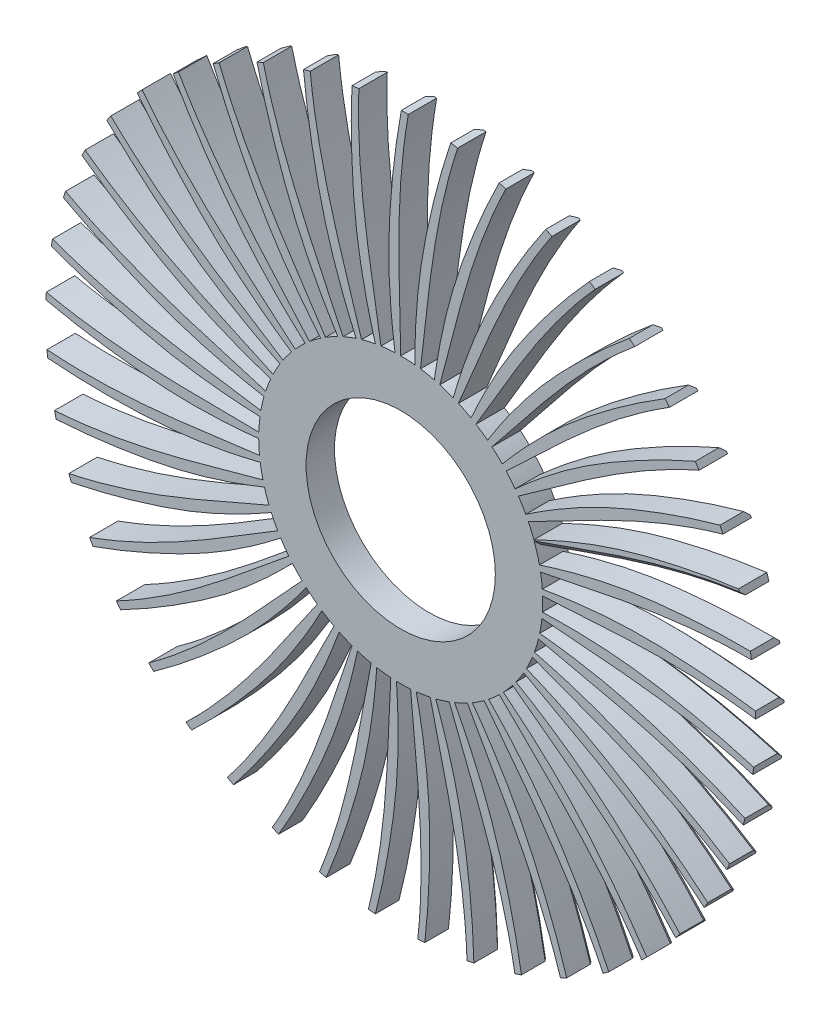
SolidWorks part; units mm, degrees
ref_plane "Front Plane" through (0, 0, 0) normal (0, 0, 1) x (1, 0, 0)
ref_plane "Top Plane" through (0, 0, 0) normal (0, 1, 0) x (1, 0, 0)
ref_plane "Right Plane" through (0, 0, 0) normal (1, 0, 0) x (0, 0, -1)
sketch "Sketch2" plane through (0, 0, 0) normal (0, 0, 1) x (1, 0, 0)
  arc A0 (-367.8181, 73.0398) -> (-369.1843, 65.7869) centre (0, 0) ccw
  arc A1 (-6, 149.88) -> (-20.876, 148.5402) centre (0, 0) ccw
  arc A2 (-354.0734, 123.5194) -> (-356.4357, 116.5272) centre (0, 0) ccw
  arc A3 (-333.437, 171.5948) -> (-336.7494, 164.9994) centre (0, 0) ccw
  arc A4 (-273.2223, 256.8552) -> (-278.2243, 251.4284) centre (0, 0) ccw
  arc A5 (-234.816, 292.3807) -> (-240.5246, 287.7028) centre (0, 0) ccw
  arc A6 (-191.8392, 322.2153) -> (-198.1433, 318.3775) centre (0, 0) ccw
  arc A7 (-145.1286, 345.7784) -> (-151.9054, 342.8553) centre (0, 0) ccw
  arc A8 (-95.5931, 362.6113) -> (-102.7109, 360.6598) centre (0, 0) ccw
  arc A9 (-44.1971, 372.3864) -> (-51.5172, 371.4445) centre (0, 0) ccw
  arc A10 (8.0592, 374.9134) -> (0.6793, 374.9994) centre (0, 0) ccw
  arc A11 (60.1586, 370.1431) -> (52.8625, 371.2554) centre (0, 0) ccw
  arc A12 (111.0871, 358.1685) -> (104.0168, 360.2853) centre (0, 0) ccw
  arc A13 (159.8535, 339.2224) -> (153.1465, 342.3027) centre (0, 0) ccw
  arc A14 (205.5084, 313.6739) -> (199.2955, 317.6576) centre (0, 0) ccw
  arc A15 (247.1634, 282.02) -> (241.5653, 286.8296) centre (0, 0) ccw
  arc A16 (284.0076, 244.8769) -> (279.1334, 250.4188) centre (0, 0) ccw
  arc A17 (315.3239, 202.9675) -> (311.2684, 209.1338) centre (0, 0) ccw
  arc A18 (340.5028, 157.1076) -> (337.345, 163.7784) centre (0, 0) ccw
  arc A19 (359.0543, 108.1898) -> (356.8555, 115.2352) centre (0, 0) ccw
  arc A20 (370.6171, 57.1662) -> (369.4203, 64.449) centre (0, 0) ccw
  arc A21 (372.0172, -47.2042) -> (372.8741, -39.8737) centre (0, 0) ccw
  arc A22 (374.9663, 5.03) -> (374.7947, 12.4084) centre (0, 0) ccw
  arc A23 (361.8272, -98.5196) -> (363.696, -91.3797) centre (0, 0) ccw
  arc A24 (344.5946, -147.9174) -> (347.4389, -141.1071) centre (0, 0) ccw
  arc A25 (320.6549, -194.4362) -> (324.4194, -188.088) centre (0, 0) ccw
  arc A26 (254.6394, -275.2885) -> (260.0078, -270.2238) centre (0, 0) ccw
  arc A27 (290.474, -237.1705) -> (295.0853, -231.408) centre (0, 0) ccw
  arc A28 (213.8485, -308.0484) -> (219.8696, -303.7801) centre (0, 0) ccw
  arc A29 (168.8953, -334.8124) -> (175.4518, -331.4237) centre (0, 0) ccw
  arc A30 (120.6547, -355.0598) -> (127.619, -352.6165) centre (0, 0) ccw
  arc A31 (-300.3975, -224.469) -> (-295.9218, -230.3374) centre (0, 0) ccw
  arc A32 (-350.6327, -132.9727) -> (-347.9478, -139.8474) centre (0, 0) ccw
  arc A33 (-328.7141, -180.4772) -> (-325.0986, -186.9114) centre (0, 0) ccw
  arc A34 (-373.702, -31.1741) -> (-373.0161, -38.5226) centre (0, 0) ccw
  arc A35 (70.0658, -368.3962) -> (77.3023, -366.946) centre (0, 0) ccw
  arc A36 (18.1131, -374.5623) -> (25.481, -374.1333) centre (0, 0) ccw
  arc A37 (-34.1922, -373.4379) -> (-26.8363, -374.0385) centre (0, 0) ccw
  arc A38 (-85.832, -365.045) -> (-78.6312, -366.6635) centre (0, 0) ccw
  arc A39 (-135.8011, -349.5469) -> (-128.8957, -352.1518) centre (0, 0) ccw
  arc A40 (-183.127, -327.2453) -> (-176.6513, -330.7859) centre (0, 0) ccw
  arc A41 (-226.8886, -298.5742) -> (-220.9687, -302.9816) centre (0, 0) ccw
  arc A42 (-266.234, -264.0917) -> (-260.9851, -269.2801) centre (0, 0) ccw
  arc A43 (-374.4037, 21.1386) -> (-374.7472, 13.7662) centre (0, 0) ccw
  arc A44 (-306.3106, 216.3303) -> (-310.5087, 210.2601) centre (0, 0) ccw
  arc A46 (-26.8009, 147.5863) -> (-41.3456, 144.1893) centre (0, 0) ccw
  arc A47 (-47.0801, 142.42) -> (-61.0105, 137.0318) centre (0, 0) ccw
  arc A48 (35.5449, 145.7277) -> (20.876, 148.5402) centre (0, 0) ccw
  arc A49 (14.9176, 149.2564) -> (0, 150) centre (0, 0) ccw
  arc A50 (-66.4429, 134.4817) -> (-79.4879, 127.2072) centre (0, 0) ccw
  arc A51 (-84.5126, 123.9259) -> (-96.4181, 114.9067) centre (0, 0) ccw
  arc A52 (-100.9372, 110.958) -> (-111.4717, 100.3696) centre (0, 0) ccw
  arc A53 (55.4804, 139.3626) -> (41.3456, 144.1893) centre (0, 0) ccw
  arc A54 (74.336, 130.2849) -> (61.0105, 137.0318) centre (0, 0) ccw
  arc A55 (91.7447, 118.6714) -> (79.4879, 127.2072) centre (0, 0) ccw
  arc A56 (-115.3973, 95.8304) -> (-124.3556, 83.8789) centre (0, 0) ccw
  arc A57 (-127.6113, 78.8376) -> (-134.8191, 65.7557) centre (0, 0) ccw
  arc A58 (107.3677, 104.7481) -> (96.4181, 114.9067) centre (0, 0) ccw
  arc A59 (120.901, 88.786) -> (111.4717, 100.3696) centre (0, 0) ccw
  arc A60 (132.081, 71.0958) -> (124.3556, 83.8789) centre (0, 0) ccw
  arc A61 (-137.3414, 60.3103) -> (-142.6585, 46.3525) centre (0, 0) ccw
  arc A62 (140.6902, 52.0218) -> (134.8191, 65.7557) centre (0, 0) ccw
  arc A63 (146.561, 31.9352) -> (142.6585, 46.3525) centre (0, 0) ccw
  arc A64 (-144.3984, 40.6091) -> (-147.7212, 26.0472) centre (0, 0) ccw
  arc A65 (-148.6448, 20.1175) -> (-149.9086, 5.2349) centre (0, 0) ccw
  arc A66 (-149.998, -0.7656) -> (-149.1783, -15.6793) centre (0, 0) ccw
  arc A67 (-148.4317, -21.6339) -> (-145.5444, -36.2883) centre (0, 0) ccw
  arc A68 (-143.9763, -42.081) -> (-139.0776, -56.191) centre (0, 0) ccw
  arc A69 (-136.7186, -61.7091) -> (-129.9038, -75) centre (0, 0) ccw
  arc A70 (-126.7998, -80.1361) -> (-118.2016, -92.3492) centre (0, 0) ccw
  arc A71 (-114.413, -97.0034) -> (-104.1988, -107.901) centre (0, 0) ccw
  arc A72 (-99.7993, -111.9826) -> (-88.1678, -121.3525) centre (0, 0) ccw
  arc A73 (-83.2431, -124.7821) -> (-70.4207, -132.4421) centre (0, 0) ccw
  arc A74 (-65.0667, -135.153) -> (-51.303, -140.9539) centre (0, 0) ccw
  arc A75 (-45.6238, -142.8932) -> (-31.1868, -146.7221) centre (0, 0) ccw
  arc A76 (-25.2929, -147.8522) -> (-10.4635, -149.6346) centre (0, 0) ccw
  arc A77 (-4.4697, -149.9334) -> (10.4635, -149.6346) centre (0, 0) ccw
  arc A78 (16.4405, -149.0963) -> (31.1868, -146.7221) centre (0, 0) ccw
  arc A79 (37.0307, -145.3572) -> (51.303, -140.9539) centre (0, 0) ccw
  arc A80 (56.9001, -138.789) -> (70.4207, -132.4421) centre (0, 0) ccw
  arc A81 (75.6621, -129.5193) -> (88.1678, -121.3525) centre (0, 0) ccw
  arc A82 (108.4314, -103.6467) -> (118.2016, -92.3492) centre (0, 0) ccw
  arc A83 (121.801, -87.5472) -> (129.9038, -75) centre (0, 0) ccw
  arc A84 (132.7998, -69.7438) -> (139.0776, -56.191) centre (0, 0) ccw
  arc A85 (141.2139, -50.5829) -> (145.5444, -36.2883) centre (0, 0) ccw
  arc A86 (146.8794, -30.4375) -> (149.1783, -15.6793) centre (0, 0) ccw
  arc A87 (92.9513, -117.7287) -> (104.1988, -107.901) centre (0, 0) ccw
  arc A88 (149.6861, -9.6996) -> (149.9086, 5.2349) centre (0, 0) ccw
  arc A89 (149.5793, 11.2271) -> (147.7212, 26.0472) centre (0, 0) ccw
  arc A90 (-365.7266, -82.8799) -> (-364.0246, -90.0615) centre (0, 0) ccw
  spline S0 degree 3 poles (-6, 149.88) (-14.2223, 209.3858) (-13.9632, 258.2908) (-6.2485, 332.5828) (-2.5507, 357.9172) (0.6793, 374.9994) knots 0 0 0 0 0.599001 0.688647 0.89646 0.89646 0.89646 0.89646
  spline S1 degree 3 poles (0, 150) (-1.5677, 225.8182) (-6.3003, 293.9271) (8.0592, 374.9134) knots 0 0 0 0 0.908524 0.908524 0.908524 0.908524
  spline S2 degree 3 poles (14.9176, 149.2564) (15.0569, 209.3274) (22.1198, 257.7204) (40.0988, 330.2157) (47.2865, 354.789) (52.8625, 371.2554) knots 0 0 0 0 0.599001 0.688647 0.89646 0.89646 0.89646 0.89646
  spline S3 degree 3 poles (20.876, 148.5402) (29.8753, 223.8387) (34.6678, 291.9435) (60.1586, 370.1431) knots 0 0 0 0 0.908524 0.908524 0.908524 0.908524
  spline S4 degree 3 poles (35.5449, 145.7277) (44.0431, 205.1947) (57.7723, 252.1338) (85.6658, 321.4214) (96.2034, 344.7552) (104.0168, 360.2853) knots 0 0 0 0 0.599001 0.688647 0.89646 0.89646 0.89646 0.89646
  spline S5 degree 3 poles (41.3456, 144.1893) (60.7369, 217.5025) (74.9611, 284.2775) (111.0871, 358.1685) knots 0 0 0 0 0.908524 0.908524 0.908524 0.908524
  spline S6 degree 3 poles (55.4804, 139.3626) (72.1721, 197.0682) (92.3003, 241.6397) (129.5653, 306.371) (143.2478, 328.0111) (153.1465, 342.3027) knots 0 0 0 0 0.599001 0.688647 0.89646 0.89646 0.89646 0.89646
  spline S7 degree 3 poles (61.0105, 137.0318) (90.4163, 206.9328) (113.7953, 271.0783) (159.8535, 339.2224) knots 0 0 0 0 0.908524 0.908524 0.908524 0.908524
  spline S8 degree 3 poles (74.336, 130.2849) (98.8963, 185.1059) (125.0318, 226.4424) (170.943, 285.3574) (187.5041, 304.8827) (199.2955, 317.6576) knots 0 0 0 0 0.599001 0.688647 0.89646 0.89646 0.89646 0.89646
  spline S9 degree 3 poles (79.4879, 127.2072) (118.3359, 192.3355) (150.4147, 252.603) (205.5084, 313.6739) knots 0 0 0 0 0.908524 0.908524 0.908524 0.908524
  spline S10 degree 3 poles (91.7447, 118.6714) (123.6956, 169.5408) (155.3297, 206.8376) (208.9934, 258.7897) (228.1108, 275.8201) (241.5653, 286.8296) knots 0 0 0 0 0.599001 0.688647 0.89646 0.89646 0.89646 0.89646
  spline S11 degree 3 poles (96.4181, 114.9067) (143.9522, 173.9945) (184.1064, 229.211) (247.1634, 282.02) knots 0 0 0 0 0.908524 0.908524 0.908524 0.908524
  spline S12 degree 3 poles (107.3677, 104.7481) (146.0874, 150.6757) (182.6042, 183.2069) (242.9761, 227.1849) (264.2776, 241.3889) (279.1334, 250.4188) knots 0 0 0 0 0.599001 0.688647 0.89646 0.89646 0.89646 0.89646
  spline S13 degree 3 poles (111.4717, 100.3696) (166.7666, 152.2669) (214.2147, 201.3576) (284.0076, 244.8769) knots 0 0 0 0 0.908524 0.908524 0.908524 0.908524
  spline S14 degree 3 poles (120.901, 88.786) (165.6356, 128.8779) (206.3246, 156.0104) (272.2295, 191.1582) (295.3005, 202.2594) (311.2684, 209.1338) knots 0 0 0 0 0.599001 0.688647 0.89646 0.89646 0.89646 0.89646
  spline S15 degree 3 poles (124.3556, 83.8789) (186.3351, 127.5756) (240.1535, 169.5851) (315.3239, 202.9675) knots 0 0 0 0 0.908524 0.908524 0.908524 0.908524
  spline S16 degree 3 poles (132.081, 71.0958) (181.96, 104.5716) (226.0291, 125.7773) (296.1842, 151.4108) (320.5757, 159.1932) (337.345, 163.7784) knots 0 0 0 0 0.599001 0.688647 0.89646 0.89646 0.89646 0.89646
  spline S17 degree 3 poles (134.8191, 65.7557) (202.2768, 100.4013) (261.4181, 134.5118) (340.5028, 157.1076) knots 0 0 0 0 0.908524 0.908524 0.908524 0.908524
  spline S18 degree 3 poles (140.6902, 52.0218) (194.7428, 78.23) (241.3343, 93.096) (314.3741, 108.7164) (339.6113, 113.0284) (356.8555, 115.2352) knots 0 0 0 0 0.599001 0.688647 0.89646 0.89646 0.89646 0.89646
  spline S19 degree 3 poles (142.6585, 46.3525) (214.2814, 71.2727) (277.5944, 96.8204) (359.0543, 108.1898) knots 0 0 0 0 0.908524 0.908524 0.908524 0.908524
  spline S20 degree 3 poles (146.561, 31.9352) (203.7351, 50.3657) (251.9421, 58.6028) (326.4451, 63.906) (352.0367, 64.6636) (369.4203, 64.449) knots 0 0 0 0 0.599001 0.688647 0.89646 0.89646 0.89646 0.89646
  spline S21 degree 3 poles (147.7212, 26.0472) (222.1153, 40.7568) (288.3677, 57.2445) (370.6171, 57.1662) knots 0 0 0 0 0.908524 0.908524 0.908524 0.908524
  spline S22 degree 3 poles (149.5793, 11.2271) (208.7619, 21.5211) (257.6461, 22.9689) (332.1621, 17.8517) (357.6102, 15.0403) (374.7947, 12.4084) knots 0 0 0 0 0.599001 0.688647 0.89646 0.89646 0.89646 0.89646
  spline S23 degree 3 poles (149.9086, 5.2349) (225.6259, 9.4477) (293.5282, 16.5543) (374.9663, 5.03) knots 0 0 0 0 0.908524 0.908524 0.908524 0.908524
  spline S24 degree 3 poles (149.6861, -9.6996) (209.7254, -7.7423) (258.3354, -13.112) (331.414, -28.5501) (356.2231, -34.8758) (372.8741, -39.8737) knots 0 0 0 0 0.599001 0.688647 0.89646 0.89646 0.89646 0.89646
  spline S25 degree 3 poles (149.1783, -15.6793) (224.745, -22.0453) (292.9755, -24.458) (372.0172, -47.2042) knots 0 0 0 0 0.908524 0.908524 0.908524 0.908524
  spline S26 degree 3 poles (146.8794, -30.4375) (206.6068, -36.8551) (253.9964, -48.9378) (324.2153, -74.3961) (347.9026, -84.1131) (363.696, -91.3797) knots 0 0 0 0 0.599001 0.688647 0.89646 0.89646 0.89646 0.89646
  spline S27 degree 3 poles (145.5444, -36.2883) (219.4897, -53.1092) (286.7204, -64.9943) (361.8272, -98.5196) knots 0 0 0 0 0.908524 0.908524 0.908524 0.908524
  spline S28 degree 3 poles (141.2139, -50.5829) (199.4669, -65.2506) (244.7137, -83.811) (310.7061, -118.7942) (332.8106, -131.7132) (347.4389, -141.1071) knots 0 0 0 0 0.599001 0.688647 0.89646 0.89646 0.89646 0.89646
  spline S29 degree 3 poles (139.0776, -56.191) (209.9623, -83.1394) (274.8846, -104.2655) (344.5946, -147.9174) knots 0 0 0 0 0.908524 0.908524 0.908524 0.908524
  spline S30 degree 3 poles (132.7998, -69.7438) (188.4446, -92.376) (230.668, -117.0529) (291.1494, -160.88) (311.2408, -176.7496) (324.4194, -188.088) knots 0 0 0 0 0.599001 0.688647 0.89646 0.89646 0.89646 0.89646
  spline S31 degree 3 poles (129.9038, -75) (196.3482, -111.5514) (257.6985, -141.5074) (320.6549, -194.4362) knots 0 0 0 0 0.908524 0.908524 0.908524 0.908524
  spline S32 degree 3 poles (121.801, -87.5472) (173.7544, -117.7034) (212.1325, -148.0165) (265.9258, -199.8345) (283.613, -218.3459) (295.0853, -231.408) knots 0 0 0 0 0.599001 0.688647 0.89646 0.89646 0.89646 0.89646
  spline S33 degree 3 poles (118.2016, -92.3492) (178.9124, -137.7922) (235.4966, -175.9949) (290.474, -237.1705) knots 0 0 0 0 0.908524 0.908524 0.908524 0.908524
  spline S34 degree 3 poles (108.4314, -103.6467) (155.6823, -140.7399) (189.4681, -176.0992) (235.5262, -234.8994) (250.465, -255.6922) (260.0078, -270.2238) knots 0 0 0 0 0.599001 0.688647 0.89646 0.89646 0.89646 0.89646
  spline S35 degree 3 poles (104.1988, -107.901) (157.9942, -161.351) (208.711, -207.0569) (254.6394, -275.2885) knots 0 0 0 0 0.908524 0.908524 0.908524 0.908524
  spline S36 degree 3 poles (92.9513, -117.7287) (134.58, -161.037) (163.116, -200.7543) (200.5424, -265.3923) (212.4421, -288.0618) (219.8696, -303.7801) knots 0 0 0 0 0.599001 0.688647 0.89646 0.89646 0.89646 0.89646
  spline S37 degree 3 poles (88.1678, -121.3525) (134.0009, -181.7692) (177.863, -234.0888) (213.8485, -308.0484) knots 0 0 0 0 0.908524 0.908524 0.908524 0.908524
  spline S38 degree 3 poles (75.6621, -129.5193) (110.8583, -178.1997) (133.589, -221.5019) (161.6553, -290.7197) (170.2841, -314.8247) (175.4518, -331.4237) knots 0 0 0 0 0.599001 0.688647 0.89646 0.89646 0.89646 0.89646
  spline S39 degree 3 poles (70.4207, -132.4421) (107.3995, -198.6496) (143.5532, -256.5644) (168.8953, -334.8124) knots 0 0 0 0 0.908524 0.908524 0.908524 0.908524
  spline S40 degree 3 poles (56.9001, -138.789) (84.9788, -191.8939) (101.4618, -237.9382) (119.6217, -310.3885) (124.8118, -335.4598) (127.619, -352.6165) knots 0 0 0 0 0.599001 0.688647 0.89646 0.89646 0.89646 0.89646
  spline S41 degree 3 poles (51.303, -140.9539) (78.7076, -211.6635) (106.4493, -274.0463) (120.6547, -355.0598) knots 0 0 0 0 0.908524 0.908524 0.908524 0.908524
  spline S42 degree 3 poles (37.0307, -145.3572) (57.4453, -201.8532) (67.3597, -249.7434) (75.2598, -324.0159) (76.9102, -349.5656) (77.3023, -366.946) knots 0 0 0 0 0.599001 0.688647 0.89646 0.89646 0.89646 0.89646
  spline S43 degree 3 poles (31.1868, -146.7221) (48.4837, -220.5576) (67.2735, -286.1942) (70.0658, -368.3962) knots 0 0 0 0 0.908524 0.908524 0.908524 0.908524
  spline S44 degree 3 poles (16.4405, -149.0963) (28.7937, -207.8836) (31.9466, -256.6876) (29.4331, -331.3368) (27.5116, -356.8674) (25.481, -374.1333) knots 0 0 0 0 0.599001 0.688647 0.89646 0.89646 0.89646 0.89646
  spline S45 degree 3 poles (10.4635, -149.6346) (17.3162, -225.1587) (26.7882, -292.7716) (18.1131, -374.5623) knots 0 0 0 0 0.908524 0.908524 0.908524 0.908524
  spline S46 degree 3 poles (-4.4697, -149.9334) (-0.4183, -209.8678) (-4.0883, -258.6356) (-16.9665, -332.2085) (-22.4225, -357.2233) (-26.8363, -374.0385) knots 0 0 0 0 0.599001 0.688647 0.89646 0.89646 0.89646 0.89646
  spline S47 degree 3 poles (-10.4635, -149.6346) (-14.1884, -225.3775) (-14.2184, -293.6506) (-34.1922, -373.4379) knots 0 0 0 0 0.908524 0.908524 0.908524 0.908524
  spline S48 degree 3 poles (-25.2929, -147.8522) (-29.6222, -207.7672) (-40.0436, -255.5496) (-63.0359, -326.6142) (-71.9202, -350.6262) (-78.6312, -366.6635) knots 0 0 0 0 0.599001 0.688647 0.89646 0.89646 0.89646 0.89646
  spline S49 degree 3 poles (-31.1868, -146.7221) (-45.4168, -221.2095) (-54.9483, -288.814) (-85.832, -365.045) knots 0 0 0 0 0.908524 0.908524 0.908524 0.908524
  spline S50 degree 3 poles (-45.6238, -142.8932) (-58.2495, -201.6226) (-75.2195, -247.4896) (-107.8783, -314.6627) (-120.018, -337.2046) (-128.8957, -352.1518) knots 0 0 0 0 0.599001 0.688647 0.89646 0.89646 0.89646 0.89646
  spline S51 degree 3 poles (-51.303, -140.9539) (-75.7612, -212.7359) (-94.6087, -278.356) (-135.8011, -349.5469) knots 0 0 0 0 0.908524 0.908524 0.908524 0.908524
  spline S52 degree 3 poles (-65.0667, -135.153) (-85.7431, -191.5537) (-108.9314, -234.6125) (-150.621, -296.5867) (-165.7798, -317.2197) (-176.6513, -330.7859) knots 0 0 0 0 0.599001 0.688647 0.89646 0.89646 0.89646 0.89646
  spline S53 degree 3 poles (-70.4207, -132.4421) (-104.631, -200.1216) (-132.4276, -262.48) (-183.127, -327.2453) knots 0 0 0 0 0.908524 0.908524 0.908524 0.908524
  spline S54 degree 3 poles (-83.2431, -124.7821) (-111.5678, -177.7563) (-140.523, -217.169) (-190.4321, -272.7379) (-208.3149, -291.0604) (-220.9687, -302.9816) knots 0 0 0 0 0.599001 0.688647 0.89646 0.89646 0.89646 0.89646
  spline S55 degree 3 poles (-88.1678, -121.3525) (-131.4643, -183.6122) (-167.669, -241.4952) (-226.8886, -298.5742) knots 0 0 0 0 0.908524 0.908524 0.908524 0.908524
  spline S56 degree 3 poles (-99.7993, -111.9826) (-135.2209, -160.4992) (-169.3796, -195.4985) (-226.5366, -243.5806) (-246.7954, -259.236) (-260.9851, -269.2801) knots 0 0 0 0 0.599001 0.688647 0.89646 0.89646 0.89646 0.89646
  spline S57 degree 3 poles (-104.1988, -107.901) (-155.7387, -163.5291) (-199.6469, -215.81) (-266.234, -264.0917) knots 0 0 0 0 0.908524 0.908524 0.908524 0.908524
  spline S58 degree 3 poles (-114.413, -97.0034) (-156.2421, -140.1181) (-194.9393, -170.0228) (-258.2318, -209.6823) (-280.4722, -222.3658) (-295.9218, -230.3374) knots 0 0 0 0 0.599001 0.688647 0.89646 0.89646 0.89646 0.89646
  spline S59 degree 3 poles (-118.2016, -92.3492) (-176.982, -140.263) (-227.7389, -185.9243) (-300.3975, -224.469) knots 0 0 0 0 0.908524 0.908524 0.908524 0.908524
  spline S60 degree 3 poles (-126.7998, -80.1361) (-174.2222, -117.0098) (-216.7048, -141.2379) (-284.9009, -171.7028) (-308.6901, -181.1676) (-325.0986, -186.9114) knots 0 0 0 0 0.599001 0.688647 0.89646 0.89646 0.89646 0.89646
  spline S61 degree 3 poles (-129.9038, -75) (-194.7804, -114.2668) (-251.3982, -152.4198) (-328.7141, -180.4772) knots 0 0 0 0 0.908524 0.908524 0.908524 0.908524
  spline S62 degree 3 poles (-136.7186, -61.7091) (-188.8113, -91.624) (-234.2523, -109.7039) (-306.0246, -130.3812) (-330.8996, -136.4431) (-347.9478, -139.8474) knots 0 0 0 0 0.599001 0.688647 0.89646 0.89646 0.89646 0.89646
  spline S63 degree 3 poles (-139.0776, -56.191) (-208.7877, -86.0466) (-270.1643, -115.9485) (-350.6327, -132.9727) knots 0 0 0 0 0.908524 0.908524 0.908524 0.908524
  spline S64 degree 3 poles (-143.9763, -42.081) (-199.7254, -64.4549) (-247.2404, -76.0346) (-321.192, -86.522) (-346.6685, -89.063) (-364.0246, -90.0615) knots 0 0 0 0 0.599001 0.688647 0.89646 0.89646 0.89646 0.89646
  spline S65 degree 3 poles (-145.5444, -36.2883) (-218.7311, -56.1515) (-283.672, -77.2205) (-365.7266, -82.8799) knots 0 0 0 0 0.908524 0.908524 0.908524 0.908524
  spline S66 degree 3 poles (-148.4317, -21.6339) (-206.7521, -36.0312) (-255.4163, -40.8855) (-330.1077, -40.9787) (-355.6899, -39.9493) (-373.0161, -38.5226) knots 0 0 0 0 0.599001 0.688647 0.89646 0.89646 0.89646 0.89646
  spline S67 degree 3 poles (-149.1783, -15.6793) (-224.4173, -25.1636) (-291.6584, -36.9895) (-373.702, -31.1741) knots 0 0 0 0 0.908524 0.908524 0.908524 0.908524
  spline S68 degree 3 poles (-149.998, -0.7656) (-209.7546, -6.9062) (-258.6207, -4.9405) (-332.5983, 5.3622) (-357.7882, 9.942) (-374.7472, 13.7662) knots 0 0 0 0 0.599001 0.688647 0.89646 0.89646 0.89646 0.89646
  spline S69 degree 3 poles (-149.9086, 5.2349) (-225.7353, 6.3141) (-293.9679, 3.9615) (-374.4037, 21.1386) knots 0 0 0 0 0.908524 0.908524 0.908524 0.908524
  spline S70 degree 3 poles (-148.6448, 20.1175) (-208.6744, 22.3532) (-256.7914, 31.1006) (-328.6152, 51.5988) (-352.9226, 59.6397) (-369.1843, 65.7869) knots 0 0 0 0 0.599001 0.688647 0.89646 0.89646 0.89646 0.89646
  spline S71 degree 3 poles (-147.7212, 26.0472) (-222.6597, 37.669) (-290.5557, 44.8353) (-367.8181, 73.0398) knots 0 0 0 0 0.908524 0.908524 0.908524 0.908524
  spline S72 degree 3 poles (-144.3984, 40.6091) (-203.5327, 51.1775) (-249.964, 66.5364) (-318.2359, 96.831) (-341.1877, 108.1766) (-356.4357, 116.5272) knots 0 0 0 0 0.599001 0.688647 0.89646 0.89646 0.89646 0.89646
  spline S73 degree 3 poles (-142.6585, 46.3525) (-215.2503, 68.2906) (-281.4882, 84.8366) (-354.0734, 123.5194) knots 0 0 0 0 0.908524 0.908524 0.908524 0.908524
  spline S74 degree 3 poles (-137.3414, 60.3103) (-194.4294, 79.0057) (-238.2713, 100.6772) (-301.6626, 140.1785) (-322.812, 154.608) (-336.7494, 164.9994) knots 0 0 0 0 0.599001 0.688647 0.89646 0.89646 0.89646 0.89646
  spline S75 degree 3 poles (-134.8191, 65.7557) (-203.6513, 97.5831) (-266.9418, 123.1865) (-333.437, 171.5948) knots 0 0 0 0 0.908524 0.908524 0.908524 0.908524
  spline S76 degree 3 poles (-127.6113, 78.8376) (-181.5417, 105.2962) (-221.9409, 132.8583) (-279.2178, 180.7977) (-298.1532, 198.0301) (-310.5087, 210.2601) knots 0 0 0 0 0.599001 0.688647 0.89646 0.89646 0.89646 0.89646
  spline S77 degree 3 poles (-124.3556, 83.8789) (-188.0884, 124.9762) (-247.1997, 159.1388) (-306.3106, 216.3303) knots 0 0 0 0 0.908524 0.908524 0.908524 0.908524
  spline S78 degree 3 poles (-115.3973, 95.8304) (-165.1206, 129.5372) (-201.2907, 162.4536) (-251.3383, 217.8978) (-267.6911, 237.5978) (-278.2243, 251.4284) knots 0 0 0 0 0.599001 0.688647 0.89646 0.89646 0.89646 0.89646
  spline S79 degree 3 poles (-111.4717, 100.3696) (-168.8646, 149.9368) (-222.6461, 191.9936) (-273.2223, 256.8552) knots 0 0 0 0 0.908524 0.908524 0.908524 0.908524
  spline S80 degree 3 poles (-100.9372, 110.958) (-145.4855, 151.2569) (-176.7225, 188.8868) (-218.5668, 250.7567) (-232.0187, 272.5409) (-240.5246, 287.7028) knots 0 0 0 0 0.599001 0.688647 0.89646 0.89646 0.89646 0.89646
  spline S81 degree 3 poles (-96.4181, 114.9067) (-146.3541, 171.979) (-193.759, 221.1115) (-234.816, 292.3807) knots 0 0 0 0 0.908524 0.908524 0.908524 0.908524
  spline S82 degree 3 poles (-84.5126, 123.9259) (-123.0188, 170.0325) (-148.7147, 211.6436) (-181.5411, 278.735) (-191.8304, 302.1793) (-198.1433, 318.3775) knots 0 0 0 0 0.599001 0.688647 0.89646 0.89646 0.89646 0.89646
  spline S83 degree 3 poles (-79.4879, 127.2072) (-120.9949, 190.6739) (-161.1006, 245.9257) (-191.8392, 322.2153) knots 0 0 0 0 0.908524 0.908524 0.908524 0.908524
  spline S84 degree 3 poles (-66.4429, 134.4817) (-98.1576, 185.4987) (-117.8123, 230.281) (-140.9819, 301.288) (-147.9083, 325.9362) (-151.9054, 342.8553) knots 0 0 0 0 0.599001 0.688647 0.89646 0.89646 0.89646 0.89646
  spline S85 degree 3 poles (-61.0105, 137.0318) (-93.2807, 205.6575) (-125.3065, 265.9532) (-145.1286, 345.7784) knots 0 0 0 0 0.908524 0.908524 0.908524 0.908524
  spline S86 degree 3 poles (-47.0801, 142.42) (-71.3859, 197.3543) (-84.6169, 244.4362) (-97.6787, 317.9768) (-101.1073, 343.349) (-102.7109, 360.6598) knots 0 0 0 0 0.599001 0.688647 0.89646 0.89646 0.89646 0.89646
  spline S87 degree 3 poles (-41.3456, 144.1893) (-63.7509, 216.6382) (-87.0735, 280.8043) (-95.5931, 362.6113) knots 0 0 0 0 0.908524 0.908524 0.908524 0.908524
  spline S88 degree 3 poles (-26.8009, 147.5863) (-43.2248, 205.3687) (-49.7744, 253.8338) (-52.4743, 328.4765) (-52.3384, 354.079) (-51.5172, 371.4445) knots 0 0 0 0 0.599001 0.688647 0.89646 0.89646 0.89646 0.89646
  spline S89 degree 3 poles (-20.876, 148.5402) (-32.9803, 223.4023) (-47.1457, 290.1898) (-44.1971, 372.3864) knots 0 0 0 0 0.908524 0.908524 0.908524 0.908524
  point P230 (0, 0)
  dimension "D2" = 300
  dimension "D3" = 45
extrude "Boss-Extrude1" add sketch "Sketch2" along normal blind 30
chamfer "Chamfer1" distance 5 angle 45 45 edges
sketch "Sketch4" plane through (0, 0, 30) normal (0, 0, 1) x (1, 0, 0)
  circle A0 centre (0, 0) radius 100
  dimension "D1" = 200
extrude "Cut-Extrude4" cut sketch "Sketch4" against normal blind 30
